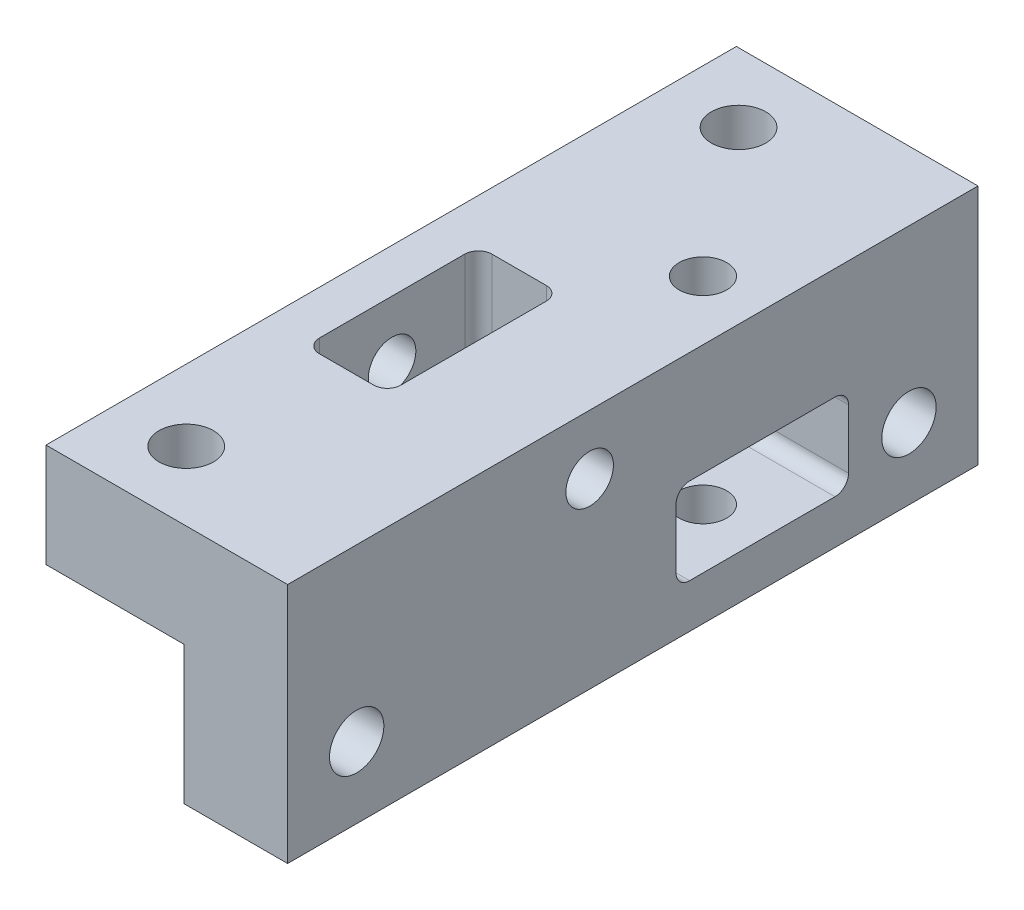
SolidWorks part; units mm, degrees
ref_plane "Front Plane" through (0, 0, 0) normal (1, 0, 0) x (0, 1, 0)
ref_plane "Top Plane" through (0, 0, 0) normal (0, 0, 1) x (0, 1, 0)
ref_plane "Right Plane" through (0, 0, 0) normal (0, 1, 0) x (-1, 0, 0)
sketch "Sketch2" plane through (0, 0, 0) normal (0, 0, 1) x (0, 1, 0)
  line L0 (0, 0) -> (-17.78, 0)
  line L1 (-17.78, 0) -> (-17.78, 7.62)
  line L2 (-17.78, 7.62) -> (-7.62, 7.62)
  line L3 (-7.62, 7.62) -> (-7.62, 17.78)
  line L4 (-7.62, 17.78) -> (0, 17.78)
  line L5 (0, 17.78) -> (0, 0)
  line L7 (-60.1663, 60.1662) -> (3.3337, 60.1662) construction
  line L8 (-60.1663, 60.1662) -> (-60.1663, -3.3338) construction
  line L9 (-60.1663, -3.3338) -> (3.3338, -3.3338) construction
  line L10 (3.3337, 60.1662) -> (3.3338, -3.3338) construction
  line L11 (-56.8325, 56.8325) -> (0, 56.8325) construction
  line L12 (-56.8325, 56.8325) -> (-56.8325, 0) construction
  line L13 (-56.8325, 0) -> (0, 0) construction
  line L14 (0, 56.8325) -> (0, 0) construction
  line L15 (-47.4663, 47.4662) -> (-9.3662, 47.4662) construction
  line L16 (-47.4663, 47.4662) -> (-47.4663, 9.3662) construction
  line L17 (-47.4663, 9.3662) -> (-9.3662, 9.3662) construction
  line L18 (-9.3662, 47.4662) -> (-9.3662, 9.3662) construction
  line L19 (-13.3662, 9.3662) -> (-9.3662, 9.3662) construction
  line L20 (-13.3662, 9.3662) -> (-13.3662, -0.6338) construction
  line L21 (-13.3662, -0.6338) -> (-9.3662, -0.6338) construction
  line L22 (-9.3662, 9.3662) -> (-9.3662, -0.6338) construction
  point P15 (-28.4163, 60.1662)
  point P16 (-28.4163, 56.8325)
  point P17 (-56.8325, 28.4162)
  point P18 (-60.1663, 28.4162)
  point P19 (-28.4163, 47.4662)
  point P24 (-47.4662, 28.4162)
  point P25 (-11.3662, -0.6338)
  point P31 (-9.3662, 4.3662)
  dimension "D1" = 17.78
  dimension "D2" = 17.78
  dimension "D3" = 63.5
  dimension "D4" = 56.8325
  dimension "D5" = 38.1
  dimension "D6" = 38.1
  dimension "D7" = 4
  dimension "D8" = 10
  dimension "D9" = 16.7
  dimension "D10" = 7.62
extrude "Boss-Extrude2" add sketch "Sketch2" along normal blind 50.8
sketch "Sketch3" plane through (0, 0, 0) normal (0, 1, 0) x (-1, 0, 0)
  line L0 (9.3662, 0) -> (-0.6338, 0) construction
  line L1 (9.3662, 0) -> (-0.6338, 0) construction
  circle A0 centre (4.3662, 15.875) radius 1.75
  point P4 (4.3662, 0)
  point P5 (0, 0)
  dimension "D1" = 3.5
  dimension "D2" = 15.875
extrude "Cut-Extrude1" cut sketch "Sketch3" against normal blind 76.2
sketch "Sketch4" plane through (-7.62, 0, 0) normal (-1, 0, 0) x (0, -1, 0)
  line L1 (8.1912, 22.225) -> (14.5412, 22.225)
  line L2 (8.1912, 22.225) -> (8.1912, 9.525)
  line L3 (8.1912, 9.525) -> (14.5412, 9.525)
  line L4 (14.5412, 22.225) -> (14.5412, 9.525)
  line L5 (17.78, 14.125) -> (17.78, 17.625) construction
  line L6 (17.78, 14.125) -> (17.78, 17.625) construction
  line L8 (7.62, 0) -> (17.78, 0) construction
  line L9 (13.3662, 0) -> (9.3662, 0) construction
  line L10 (13.3662, 0) -> (9.3662, 0) construction
  line L11 (7.62, 50.8) -> (17.78, 50.8) construction
  circle A0 centre (12.5412, 5.08) radius 2
  circle A1 centre (12.5412, 5.08) radius 3.6 construction
  circle A2 centre (12.5412, 45.72) radius 2
  point P6 (14.5412, 15.875)
  point P9 (17.78, 15.875)
  point P10 (12.5412, 8.68)
  point P14 (12.5412, 7.08)
  point P15 (11.3662, 0)
  point P16 (0, 0)
  point P18 (-3.3338, 0)
  point P24 (11.3662, 9.525)
  dimension "D3" = 4
  dimension "D1" = 6.35
  dimension "D2" = 12.7
  dimension "D4" = 1.6
  dimension "D5" = 15.875
  dimension "D6" = 5.08
  dimension "D7" = 5.08
extrude "Cut-Extrude2" cut sketch "Sketch4" against normal blind 76.2
sketch "Sketch6" plane through (-17.78, 0, 0) normal (-1, 0, 0) x (0, -1, 0)
  line L0 (0, 50.8) -> (0, 0) construction
  line L1 (0, 0) -> (7.62, 0) construction
  circle A0 centre (4.3663, 28.575) radius 1.75
  dimension "D2" = 3.5
  dimension "D1" = 4.3663
  dimension "D3" = 28.575
extrude "Cut-Extrude3" cut sketch "Sketch6" against normal blind 76.2
sketch "Sketch7" plane through (0, -7.62, 0) normal (0, -1, 0) x (1, 0, 0)
  line L0 (-17.78, 50.8) -> (-17.78, 0) construction
  line L1 (-14.5412, 34.925) -> (-8.5412, 34.925)
  line L2 (-14.5412, 34.925) -> (-14.5412, 22.225)
  line L3 (-14.5412, 22.225) -> (-8.5412, 22.225)
  line L4 (-8.5412, 34.925) -> (-8.5412, 22.225)
  line L5 (-17.78, 30.325) -> (-17.78, 26.825) construction
  line L6 (-17.78, 30.325) -> (-17.78, 26.825) construction
  line L7 (-7.62, 47.72) -> (-7.62, 43.72) construction
  line L8 (-7.62, 7.08) -> (-7.62, 3.08) construction
  line L9 (-7.62, 47.72) -> (-7.62, 43.72) construction
  line L10 (-7.62, 7.08) -> (-7.62, 3.08) construction
  circle A0 centre (-12.5412, 45.72) radius 2
  circle A1 centre (-12.5412, 5.08) radius 2
  point P8 (-17.78, 28.575)
  point P9 (-14.5412, 28.575)
  point P18 (-7.62, 5.08)
  point P20 (0, 0)
  point P21 (-7.62, 45.72)
  point P22 (0, 0)
  point P23 (0, 0)
  dimension "D5" = 4
  dimension "D1" = 6
  dimension "D2" = 3.2388
  dimension "D3" = 12.7
  dimension "D4" = 15.875
extrude "Cut-Extrude4" cut sketch "Sketch7" against normal blind 76.2
fillet "Fillet1" radius 1 8 edges at (-3.81, -14.5412, 9.525) (-3.81, -14.5412, 22.225) (-3.81, -8.1912, 22.225) (-3.81, -8.1912, 9.525) (-8.5412, -3.81, 22.225) (-14.5412, -3.81, 22.225) (-8.5412, -3.81, 34.925) (-14.5412, -3.81, 34.925)
